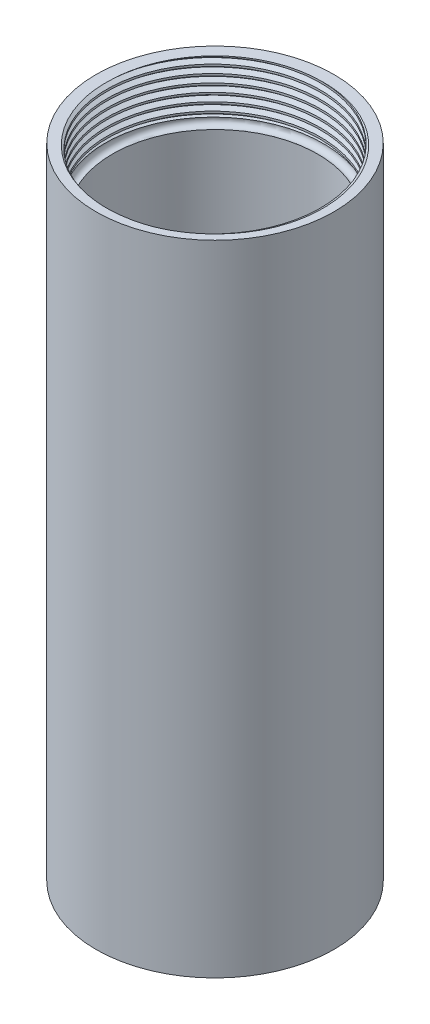
SolidWorks part; units mm, degrees
other "Marcação1"
sketch "Esboço95" plane through (-36.5, 0, -36.5) normal (-0.6691, 0.7292, -0.1437) x (0.7423, 0.6461, -0.1775)
material "1.0401 (C15)"
ref_plane "Plano frontal" through (0, 0, 0) normal (0, 0, 1) x (1, 0, 0)
ref_plane "Plano superior" through (0, 0, 0) normal (0, 1, 0) x (1, 0, 0)
ref_plane "Plano direito" through (0, 0, 0) normal (1, 0, 0) x (0, 0, -1)
sketch "Esboço1" plane through (0, 0, 0) normal (0, 1, 0) x (1, 0, 0)
  circle A0 centre (0, 0) radius 31.5
  circle A1 centre (0, 0) radius 36.5
  dimension "D1" = 63
  dimension "D3" = 5
extrude "cilíndro" add sketch "Esboço1" against normal blind 196
ref_plane "plano-grelha" through (0, -164, 0) normal (0, -1, 0) x (-1, 0, 0)
sketch "Esboço256" plane through (0, -164, 0) normal (0, -1, 0) x (-1, 0, 0)
  circle A0 centre (0, 0) radius 32.8
  dimension "D1" = 65.6
extrude "grelha" cut sketch "Esboço256" along normal blind 7
ref_plane "plano-anel-tubeira" through (0, -172.27, 0) normal (0, -1, 0) x (-1, 0, 0)
sketch "Esboço10" plane through (0, -196, 0) normal (0, -1, 0) x (1, 0, 0)
  circle A0 centre (0, 0) radius 32.8
  dimension "D1" = 65.6
extrude "tubeira" cut sketch "Esboço10" against normal blind 23.73
sketch "Esboço191" plane through (0, -172.27, 0) normal (0, -1, 0) x (-1, 0, 0)
  circle A0 centre (0, 0) radius 32.1
  dimension "D1" = 64.2
sweep "anel-tubeira" cut path "Esboço191" circular profile diameter 3 parameters "D3"=3
thread "rosca-tubeira" pitch 2.5 method cut trim with start face yes trim with end face yes profile "Perfil da rosca13" start angle 0, offset 2.5, length 0, pitch 2.5, diameter 65.6
ref_plane "Plano19" through (32.8, -198.5, 0) normal (0, 0, 1) x (1, 0, 0)
sketch "Perfil da rosca13" plane through (32.8, -198.5, 0) normal (0, 0, 1) x (1, 0, 0)
  line L0 (0, 0) -> (0, 2.5) construction
  line L1 (0, 0) -> (1.3532, 0.7812)
  line L2 (1.3532, 0.7812) -> (1.3532, 1.0937)
  line L3 (1.3532, 1.0937) -> (0, 1.875)
  line L4 (1.3532, 0.9375) -> (0, 0.9375) construction
  line L11 (0, 0) -> (0, 1.875)
  point P2 (0, 0)
  dimension "Pitch" = 2.5
  dimension "Profile_Angle" = 60
  dimension "Profile_Land" = 0.3125
  dimension "Profile_Height" = 1.3532
sketch "Esboço2" plane through (0, 0, 0) normal (0, 1, 0) x (1, 0, 0)
  circle A0 centre (0, 0) radius 32.8
  dimension "D1" = 65.6
extrude "suporte" cut sketch "Esboço2" along direction (0, 1, 0) on the side against the normal blind 16 contours A0
ref_plane "plano-anel-suporte" through (0, -17.27, 0) normal (0, 1, 0) x (1, 0, 0)
sketch "Esboço187" plane through (0, -17.27, 0) normal (0, 1, 0) x (1, 0, 0)
  circle A0 centre (0, 0) radius 32.1
  dimension "D1" = 64.2
sweep "anel-suporte" cut path "Esboço187" circular profile diameter 3 parameters "D3"=3
thread "rosca-suporte" pitch 2.5 method cut trim with start face yes trim with end face yes profile "Perfil da rosca14" start angle 0, offset 2.5, length 0, pitch 2.5, diameter 65.6
ref_plane "Plano21" through (-32.8, 2.5, 0) normal (0, 0, 1) x (-1, 0, 0)
sketch "Perfil da rosca14" plane through (-32.8, 2.5, 0) normal (0, 0, 1) x (-1, 0, 0)
  line L0 (0, 0) -> (0, 2.5) construction
  line L1 (0, 0) -> (1.3532, 0.7812)
  line L2 (1.3532, 0.7812) -> (1.3532, 1.0937)
  line L3 (1.3532, 1.0937) -> (0, 1.875)
  line L4 (1.3532, 0.9375) -> (0, 0.9375) construction
  line L11 (0, 0) -> (0, 1.875)
  point P2 (0, 0)
  dimension "Pitch" = 2.5
  dimension "Profile_Angle" = 60
  dimension "Profile_Land" = 0.3125
  dimension "Profile_Height" = 1.3532
